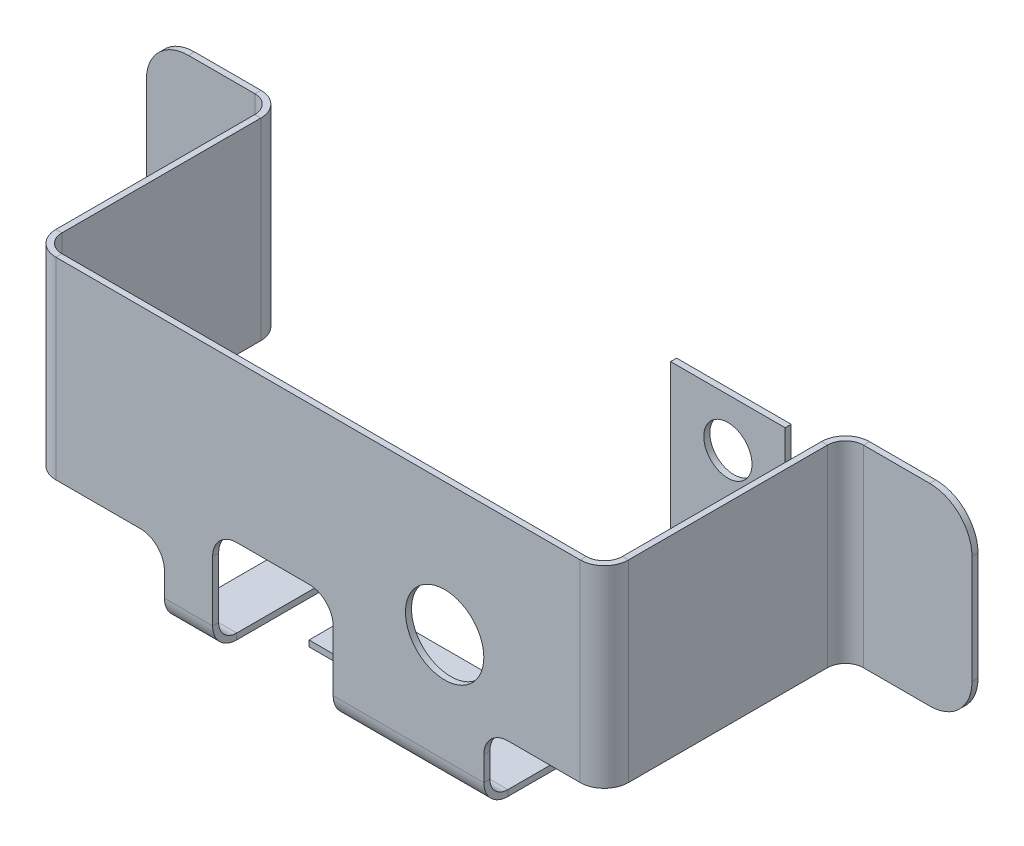
SolidWorks part; units mm, degrees
note: The reader was unsure of these and kept them because the rebuilt part matched: flange length of "Edge-Flange1", "Edge-Flange2", "Edge-Flange3", "Edge-Flange4", "Edge-Flange5".
ref_plane "Front Plane" through (0, 0, 0) normal (0, 0, 1) x (1, 0, 0)
ref_plane "Top Plane" through (0, 0, 0) normal (0, 1, 0) x (1, 0, 0)
ref_plane "Right Plane" through (0, 0, 0) normal (1, 0, 0) x (0, 0, -1)
sketch "Sketch1" plane through (0, 0, 0) normal (0, 0, 1) x (1, 0, 0)
  line L0 (-47.5, 0) -> (47.5, 0)
  line L1 (-47.5, 0) -> (-47.5, -32)
  line L2 (47.5, 0) -> (47.5, -32)
  line L3 (47.5, -32) -> (31.5, -32)
  line L4 (27.5, -36) -> (27.5, -44)
  line L5 (27.5, -44) -> (2.5, -44)
  line L6 (2.5, -44) -> (2.5, -30)
  line L7 (-1.5, -26) -> (-13.5, -26)
  line L8 (-17.5, -30) -> (-17.5, -44)
  line L9 (-17.5, -44) -> (-25.5, -44)
  line L10 (-25.5, -44) -> (-25.5, -36)
  line L11 (-47.5, -32) -> (-29.5, -32)
  arc A2 (31.5, -32) -> (27.5, -36) centre (31.5, -36) ccw
  arc A3 (2.5, -30) -> (-1.5, -26) centre (-1.5, -30) ccw
  arc A4 (-13.5, -26) -> (-17.5, -30) centre (-13.5, -30) ccw
  arc A5 (-25.5, -36) -> (-29.5, -32) centre (-29.5, -36) ccw
  point P3 (0, 0)
  point P19 (27.5, -32)
  point P22 (2.5, -26)
  point P25 (-17.5, -26)
  point P28 (-25.5, -32)
  dimension "D14" = 4
  dimension "D1" = 95
  dimension "D2" = 32
  dimension "D3" = 20
  dimension "D4" = 44
  dimension "D5" = 50
  dimension "D6" = 18
  dimension "D7" = 20
  dimension "D8" = 8
  dimension "D9" = 12
base flange "Base-Flange1" sketch "Sketch1" thickness 1 reverse thickness direction no parameters "D1"=10
sketch "Sketch6" plane through (0, 0, 0) normal (0, 0, 1) x (1, 0, 0)
  line L0 (2.5, -30) -> (2.5, -44) construction
  line L1 (47.5, 0) -> (-47.5, 0) construction
  circle A0 centre (21, -22) radius 6.5
  dimension "D1" = 13
  dimension "D3" = 18.5
  dimension "D4" = 22
extrude "Cut-Extrude1" cut sketch "Sketch6" against normal blind 10
edge flange "Edge-Flange1" sketch "Sketch13" flange angle 90 flange length 41 flange position material inside bend radius 3 thickness 1 relief rectangular parameters "D6"=10
sketch "Sketch13" plane through (47.5, 0, -1) normal (1, 0, 0) x (0, -1, 0)
  line L2 (0, 0) -> (0, 40)
  line L3 (0, 40) -> (32, 40)
  line L4 (32, 40) -> (32, 0)
  line L7 (32, 0) -> (0, 0) construction
  line L8 (32, 0) -> (0, 0)
  line L9 (32, -1) -> (0, -1) construction
  dimension "D1" = 41
bend "EdgeBend1" bend radius 3 bend angle 90 parameters "D5"=1
edge flange "Edge-Flange2" sketch "Sketch16" flange angle 90 flange length 22 flange position material inside bend radius 3 thickness 1 relief rectangular parameters "D6"=10
sketch "Sketch16" plane through (47.5, 0, -41) normal (0, 0, -1) x (0, 1, 0)
  line L2 (-32, 0) -> (-32, 14)
  line L3 (-25, 21) -> (-7, 21)
  line L4 (0, 14) -> (0, 0)
  line L11 (-32, 0) -> (0, 0) construction
  line L12 (-32, 0) -> (0, 0)
  line L13 (-32, -1) -> (0, -1) construction
  arc A0 (-7, 21) -> (0, 14) centre (-7, 14) cw
  arc A1 (-32, 14) -> (-25, 21) centre (-25, 14) cw
  dimension "D2" = 7
  dimension "D1" = 22
bend "EdgeBend2" bend radius 3 bend angle 90 parameters "D5"=2
mirror "Mirror1" about plane through (0, 0, 0) normal (1, 0, 0) of "Edge-Flange1", "Edge-Flange2"
bend "MirrorBend1" bend radius 3 bend angle 90 parameters "D5"=3
bend "MirrorBend2" bend radius 3 bend angle 90 parameters "D5"=4
edge flange "Edge-Flange3" sketch "Sketch19" flange angle 90 flange length 19 flange position material inside bend radius 3 thickness 1 relief rectangular parameters "D6"=10
sketch "Sketch19" plane through (0, -44, -1) normal (0, -1, 0) x (-1, 0, 0)
  line L2 (17.5, 0) -> (17.5, 18)
  line L3 (17.5, 18) -> (25.5, 18)
  line L4 (25.5, 18) -> (25.5, 0)
  line L7 (25.5, 0) -> (17.5, 0) construction
  line L8 (25.5, 0) -> (17.5, 0)
  line L10 (25.5, -1) -> (17.5, -1) construction
  dimension "D1" = 19
bend "EdgeBend3" bend radius 3 bend angle 90 parameters "D5"=5
edge flange "Edge-Flange4" sketch "Sketch22" flange angle 90 flange length 51 flange position material inside bend radius 3 thickness 1 relief rectangular parameters "D6"=10
sketch "Sketch22" plane through (0, -44, -1) normal (0, -1, 0) x (-1, 0, 0)
  line L0 (-2.5, -1) -> (-27.5, -1) construction
  line L2 (-27.5, 0) -> (-27.5, 50)
  line L3 (-27.5, 50) -> (-8.5, 50)
  line L4 (-2.5, 8) -> (-2.5, 0)
  line L7 (-2.5, 0) -> (-27.5, 0) construction
  line L8 (-2.5, 0) -> (-27.5, 0)
  line L9 (-8.5, 50) -> (-8.5, 18)
  line L10 (-2.5, 8) -> (10.5, 8)
  line L11 (13.5, -1) -> (1.5, -1) construction
  line L12 (-2.5, 18) -> (4.5, 18)
  line L13 (4.5, 18) -> (10.5, 14.5359)
  line L14 (10.5, 14.5359) -> (10.5, 8)
  line L15 (-2.5, 18) -> (-8.5, 18)
  dimension "D1" = 19
  dimension "D2" = 9
  dimension "D3" = 19
  dimension "D4" = 38
  dimension "D5" = 6
  dimension "D6" = 30
  dimension "D7" = 51
bend "EdgeBend4" bend radius 3 bend angle 90 parameters "D5"=6
edge flange "Edge-Flange5" sketch "Sketch25" flange angle 90 flange length 30 flange position material inside bend radius 3 thickness 1 relief rectangular parameters "D6"=10
sketch "Sketch25" plane through (0, -43, -51) normal (0, 0, -1) x (-1, 0, 0)
  line L2 (-27.5, 0) -> (-27.5, 29)
  line L3 (-27.5, 29) -> (-8.5, 29)
  line L4 (-8.5, 29) -> (-8.5, 0)
  line L7 (-8.5, 0) -> (-27.5, 0) construction
  line L8 (-8.5, 0) -> (-27.5, 0)
  line L9 (-8.5, -1) -> (-27.5, -1) construction
  circle A0 centre (-18, 21) radius 4
  point P8 (-18, 29)
  point P10 (-21, 21)
  dimension "D2" = 8
  dimension "D1" = 30
bend "EdgeBend5" bend radius 3 bend angle 90 parameters "D5"=7
sketch "Bend-Lines1" [suppressed] plane through (0, 0, 0) normal (0, 1, 0) x (1, 0, 0)
sketch "Bounding-Box1" [suppressed] plane through (0, 0, 0) normal (0, 1, 0) x (1, 0, 0)
sheet metal parameters "Sheet-Metal1" thickness 1 parameters "D1"=10
flat pattern "Flat-Pattern1" [suppressed]
sketch "Bend-Lines2" plane through (0, 0, 0) normal (0, 1, 0) x (1, 0, 0)
sketch3d "Bounding-Box2" [suppressed]
  line L0 (18, -8, 0) -> (-77, -8, 0) construction
  line L1 (18, 36, 0) -> (-77, 36, 0) construction
  line L2 (18, -8, 0) -> (18, 36, 0) construction
  line L3 (-77, -8, 0) -> (-77, 36, 0) construction
sheet metal parameters "Sheet-Metal2" thickness 1 parameters "D1"=10
flat pattern "Flat-Pattern1"
sketch "Bend-Lines2" plane through (0, 0, 0) normal (0, 1, 0) x (1, 0, 0)
sketch3d "Bounding-Box2" [suppressed]
  line L0 (-18, -8, 0) -> (77, -8, 0) construction
  line L1 (-18, 36, 0) -> (77, 36, 0) construction
  line L2 (-18, -8, 0) -> (-18, 36, 0) construction
  line L3 (77, -8, 0) -> (77, 36, 0) construction
sheet metal parameters "Sheet-Metal3" thickness 1 parameters "D1"=10
flat pattern "Flat-Pattern1"
sketch "Bend-Lines2" plane through (0, 0, 0) normal (0, 0, 1) x (1, 0, 0)
  line L0 (46.2489, -32) -> (46.2489, 0) construction
  line L1 (46.2489, -32) -> (46.2489, 0) construction
sketch3d "Bounding-Box2" [suppressed]
  line L0 (-18, -8, 0) -> (115.4978, -8, 0) construction
  line L1 (-18, 36, 0) -> (115.4978, 36, 0) construction
  line L2 (-18, -8, 0) -> (-18, 36, 0) construction
  line L3 (115.4978, -8, 0) -> (115.4978, 36, 0) construction
bend of the flat pattern "Flatten-<EdgeBend1>1"
sheet metal parameters "Sheet-Metal4" thickness 1 parameters "D1"=10
flat pattern "Flat-Pattern1"
sketch "Bend-Lines2" plane through (0, 0, 0) normal (0, 0, 1) x (1, 0, 0)
  line L0 (46.2489, -32) -> (46.2489, 0) construction
  line L1 (46.2489, -32) -> (46.2489, 0) construction
  line L2 (84.7467, -32) -> (84.7467, 0) construction
  line L3 (84.7467, -32) -> (84.7467, 0) construction
sketch3d "Bounding-Box2" [suppressed]
  line L0 (-18, -8, 0) -> (134.9956, -8, 0) construction
  line L1 (-18, 36, 0) -> (134.9956, 36, 0) construction
  line L2 (-18, -8, 0) -> (-18, 36, 0) construction
  line L3 (134.9956, -8, 0) -> (134.9956, 36, 0) construction
bend of the flat pattern "Flatten-<EdgeBend1>1"
bend of the flat pattern "Flatten-<EdgeBend2>1"
sheet metal parameters "Sheet-Metal5" thickness 1 parameters "D1"=10
flat pattern "Flat-Pattern1"
sketch "Bend-Lines2" plane through (0, 0, 0) normal (0, 0, 1) x (1, 0, 0)
  line L0 (46.2489, -32) -> (46.2489, 0) construction
  line L1 (46.2489, -32) -> (46.2489, 0) construction
  line L2 (84.7467, -32) -> (84.7467, 0) construction
  line L3 (84.7467, -32) -> (84.7467, 0) construction
  line L4 (-84.7467, 0) -> (-84.7467, -32) construction
  line L5 (-46.2489, 0) -> (-46.2489, -32) construction
  line L6 (-84.7467, 0) -> (-84.7467, -32) construction
  line L7 (-46.2489, 0) -> (-46.2489, -32) construction
sketch3d "Bounding-Box2" [suppressed]
  line L0 (-75.9956, -8, 0) -> (134.9956, -8, 0) construction
  line L1 (-75.9956, 36, 0) -> (134.9956, 36, 0) construction
  line L2 (-75.9956, -8, 0) -> (-75.9956, 36, 0) construction
  line L3 (134.9956, -8, 0) -> (134.9956, 36, 0) construction
bend of the flat pattern "Flatten-<EdgeBend1>1"
bend of the flat pattern "Flatten-<EdgeBend2>1"
bend of the flat pattern "Flatten-<MirrorBend1>1"
bend of the flat pattern "Flatten-<MirrorBend2>1"
sheet metal parameters "Sheet-Metal6" thickness 1 parameters "D1"=10
flat pattern "Flat-Pattern1"
sketch "Bend-Lines2" plane through (0, 0, 0) normal (0, 0, 1) x (1, 0, 0)
  line L0 (46.2489, -32) -> (46.2489, 0) construction
  line L1 (46.2489, -32) -> (46.2489, 0) construction
  line L2 (84.7467, -32) -> (84.7467, 0) construction
  line L3 (84.7467, -32) -> (84.7467, 0) construction
  line L4 (-84.7467, 0) -> (-84.7467, -32) construction
  line L5 (-46.2489, 0) -> (-46.2489, -32) construction
  line L6 (-84.7467, 0) -> (-84.7467, -32) construction
  line L7 (-46.2489, 0) -> (-46.2489, -32) construction
  line L8 (-25.5, -42.7489) -> (-17.5, -42.7489) construction
  line L9 (-25.5, -42.7489) -> (-17.5, -42.7489) construction
sketch3d "Bounding-Box2" [suppressed]
  line L0 (-75.9956, -24.4978, 0) -> (134.9956, -24.4978, 0) construction
  line L1 (-75.9956, 36, 0) -> (134.9956, 36, 0) construction
  line L2 (-75.9956, -24.4978, 0) -> (-75.9956, 36, 0) construction
  line L3 (134.9956, -24.4978, 0) -> (134.9956, 36, 0) construction
bend of the flat pattern "Flatten-<EdgeBend1>1"
bend of the flat pattern "Flatten-<EdgeBend2>1"
bend of the flat pattern "Flatten-<MirrorBend1>1"
bend of the flat pattern "Flatten-<MirrorBend2>1"
bend of the flat pattern "Flatten-<EdgeBend3>1"
sheet metal parameters "Sheet-Metal7" thickness 1 parameters "D1"=10
flat pattern "Flat-Pattern1"
sketch "Bend-Lines2" plane through (0, 0, 0) normal (0, 0, 1) x (1, 0, 0)
  line L0 (46.2489, -32) -> (46.2489, 0) construction
  line L1 (46.2489, -32) -> (46.2489, 0) construction
  line L2 (84.7467, -32) -> (84.7467, 0) construction
  line L3 (84.7467, -32) -> (84.7467, 0) construction
  line L4 (-84.7467, 0) -> (-84.7467, -32) construction
  line L5 (-46.2489, 0) -> (-46.2489, -32) construction
  line L6 (-84.7467, 0) -> (-84.7467, -32) construction
  line L7 (-46.2489, 0) -> (-46.2489, -32) construction
  line L8 (-25.5, -42.7489) -> (-17.5, -42.7489) construction
  line L9 (-25.5, -42.7489) -> (-17.5, -42.7489) construction
  line L10 (2.5, -42.7489) -> (27.5, -42.7489) construction
  line L11 (2.5, -42.7489) -> (27.5, -42.7489) construction
sketch3d "Bounding-Box2" [suppressed]
  line L0 (-75.9956, -56.4978, 0) -> (134.9956, -56.4978, 0) construction
  line L1 (-75.9956, 36, 0) -> (134.9956, 36, 0) construction
  line L2 (-75.9956, -56.4978, 0) -> (-75.9956, 36, 0) construction
  line L3 (134.9956, -56.4978, 0) -> (134.9956, 36, 0) construction
bend of the flat pattern "Flatten-<EdgeBend1>1"
bend of the flat pattern "Flatten-<EdgeBend2>1"
bend of the flat pattern "Flatten-<MirrorBend1>1"
bend of the flat pattern "Flatten-<MirrorBend2>1"
bend of the flat pattern "Flatten-<EdgeBend3>1"
bend of the flat pattern "Flatten-<EdgeBend4>1"
sheet metal parameters "Sheet-Metal8" thickness 1 parameters "D1"=10
flat pattern "Flat-Pattern1"
sketch "Bend-Lines2" plane through (0, 0, 0) normal (0, 0, 1) x (1, 0, 0)
  line L0 (46.2489, -32) -> (46.2489, 0) construction
  line L1 (46.2489, -32) -> (46.2489, 0) construction
  line L2 (84.7467, -32) -> (84.7467, 0) construction
  line L3 (84.7467, -32) -> (84.7467, 0) construction
  line L4 (-84.7467, 0) -> (-84.7467, -32) construction
  line L5 (-46.2489, 0) -> (-46.2489, -32) construction
  line L6 (-84.7467, 0) -> (-84.7467, -32) construction
  line L7 (-46.2489, 0) -> (-46.2489, -32) construction
  line L8 (-25.5, -42.7489) -> (-17.5, -42.7489) construction
  line L9 (-25.5, -42.7489) -> (-17.5, -42.7489) construction
  line L10 (2.5, -42.7489) -> (27.5, -42.7489) construction
  line L11 (2.5, -42.7489) -> (27.5, -42.7489) construction
  line L12 (8.5, -91.2467) -> (27.5, -91.2467) construction
  line L13 (8.5, -91.2467) -> (27.5, -91.2467) construction
sketch3d "Bounding-Box2" [suppressed]
  line L0 (-75.9956, -83.9956, 0) -> (134.9956, -83.9956, 0) construction
  line L1 (-75.9956, 36, 0) -> (134.9956, 36, 0) construction
  line L2 (-75.9956, -83.9956, 0) -> (-75.9956, 36, 0) construction
  line L3 (134.9956, -83.9956, 0) -> (134.9956, 36, 0) construction
bend of the flat pattern "Flatten-<EdgeBend1>1"
bend of the flat pattern "Flatten-<EdgeBend2>1"
bend of the flat pattern "Flatten-<MirrorBend1>1"
bend of the flat pattern "Flatten-<MirrorBend2>1"
bend of the flat pattern "Flatten-<EdgeBend3>1"
bend of the flat pattern "Flatten-<EdgeBend4>1"
bend of the flat pattern "Flatten-<EdgeBend5>1"
